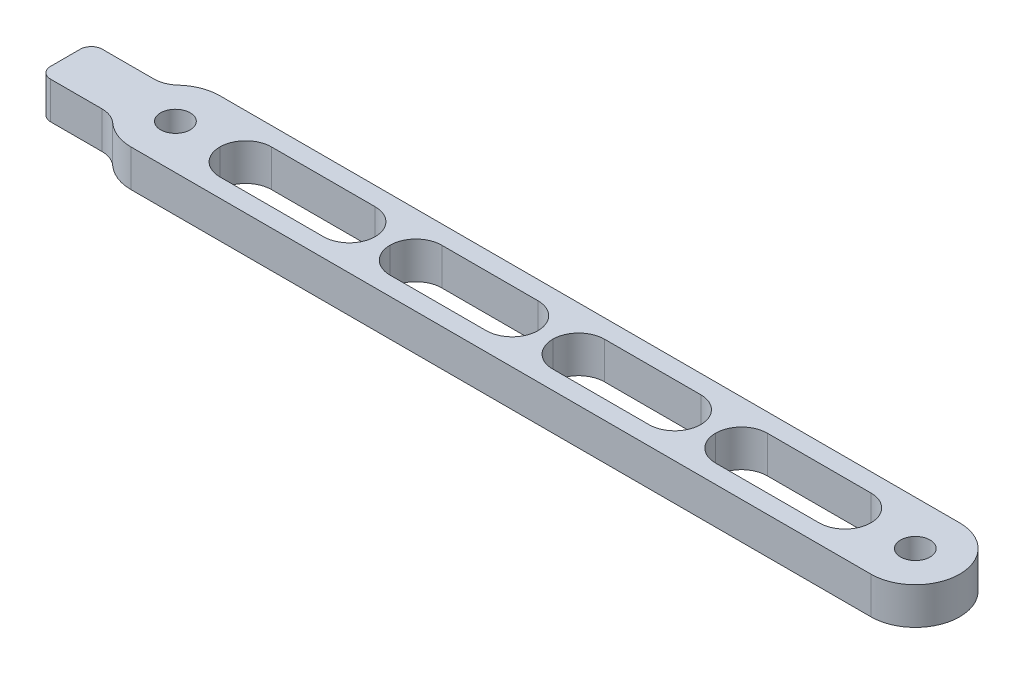
SolidWorks part; units mm, degrees
material "1060 Alloy"
ref_plane "Front Plane" through (0, 0, 0) normal (0, 0, 1) x (1, 0, 0)
ref_plane "Top Plane" through (0, 0, 0) normal (0, 1, 0) x (1, 0, 0)
ref_plane "Right Plane" through (0, 0, 0) normal (1, 0, 0) x (0, 0, -1)
sketch "Sketch1" plane through (0, 0, 0) normal (0, 1, 0) x (1, 0, 0)
  line L0 (-100, 7) -> (-100, -7) construction
  line L1 (-190.2532, -7) -> (-9.7468, -7) construction
  line L2 (-9.7468, 7) -> (-190.2532, 7) construction
  line L3 (-200, 12) -> (0, 12)
  line L4 (0, -12) -> (-200, -12)
  line L5 (-56, 7) -> (-56, -7) construction
  line L6 (-188, 0) -> (-100, 0) construction
  line L7 (-100, 0) -> (-12, 0) construction
  line L8 (-144, 7) -> (-144, -7) construction
  line L9 (-188, 7) -> (-188, -7)
  line L10 (-146, 7) -> (-146, -7)
  line L11 (-142, 7) -> (-142, -7)
  line L12 (-102, 7) -> (-102, -7)
  line L13 (-98, 7) -> (-98, -7)
  line L14 (-58, 7) -> (-58, -7)
  line L15 (-54, 7) -> (-54, -7)
  line L16 (-12, 7) -> (-12, -7)
  line L17 (-146, 7) -> (-188, 7)
  line L18 (-188, -7) -> (-146, -7)
  line L19 (-142, -7) -> (-102, -7)
  line L20 (-102, 7) -> (-142, 7)
  line L21 (-98, 7) -> (-58, 7)
  line L22 (-98, -7) -> (-58, -7)
  line L23 (-54, -7) -> (-12, -7)
  line L24 (-54, 7) -> (-12, 7)
  line L31 (-200, 0) -> (-200, -44.1421) construction
  line L32 (-200, 0) -> (-229.7468, 0) construction
  line L33 (-229.7468, 7) -> (-209.7468, 7)
  line L34 (-229.7468, 7) -> (-229.7468, -7)
  line L35 (-229.7468, -7) -> (-209.7468, -7)
  circle A0 centre (0, 0) radius 12 construction
  circle A1 centre (-200, 0) radius 12 construction
  circle A2 centre (-200, 0) radius 4
  circle A3 centre (0, 0) radius 4
  arc A5 (0, -12) -> (0, 12) centre (0, 0) ccw
  arc A7 (-200, -12) -> (-209.7468, -7) centre (-200, 0) cw
  arc A9 (-209.7468, 7) -> (-200, 12) centre (-200, 0) cw
  point P22 (-144, 0)
  point P28 (-56, 0)
  point P57 (-229.7468, 0)
  dimension "D2" = 24
  dimension "D3" = 24
  dimension "D4" = 8
  dimension "D5" = 8
  dimension "D1" = 200
  dimension "D6" = 5
  dimension "D7" = 5
  dimension "D8" = 7
  dimension "D9" = 7
  dimension "D10" = 2
  dimension "D11" = 2
  dimension "D12" = 2
  dimension "D13" = 2
  dimension "D14" = 2
  dimension "D15" = 2
  dimension "D16" = 20
extrude "Boss-Extrude1" add sketch "Sketch1" along normal blind 10
fillet "Fillet1" radius 7 18 edges at (-142, 5, -7) (-98, 5, -7) (-54, 5, -7) (-58, 5, -7) (-12, 5, -7) (-102, 5, -7) (-146, 5, -7) (-146, 5, 7) (-102, 5, 7) (-58, 5, 7) (-12, 5, 7) (-54, 5, 7) (-98, 5, 7) (-142, 5, 7) (-188, 5, 7) (-188, 5, -7) (-209.7468, 5, 7) (-209.7468, 5, -7)
fillet "Fillet2" radius 3 2 edges at (-229.7468, 5, 7) (-229.7468, 5, -7)
